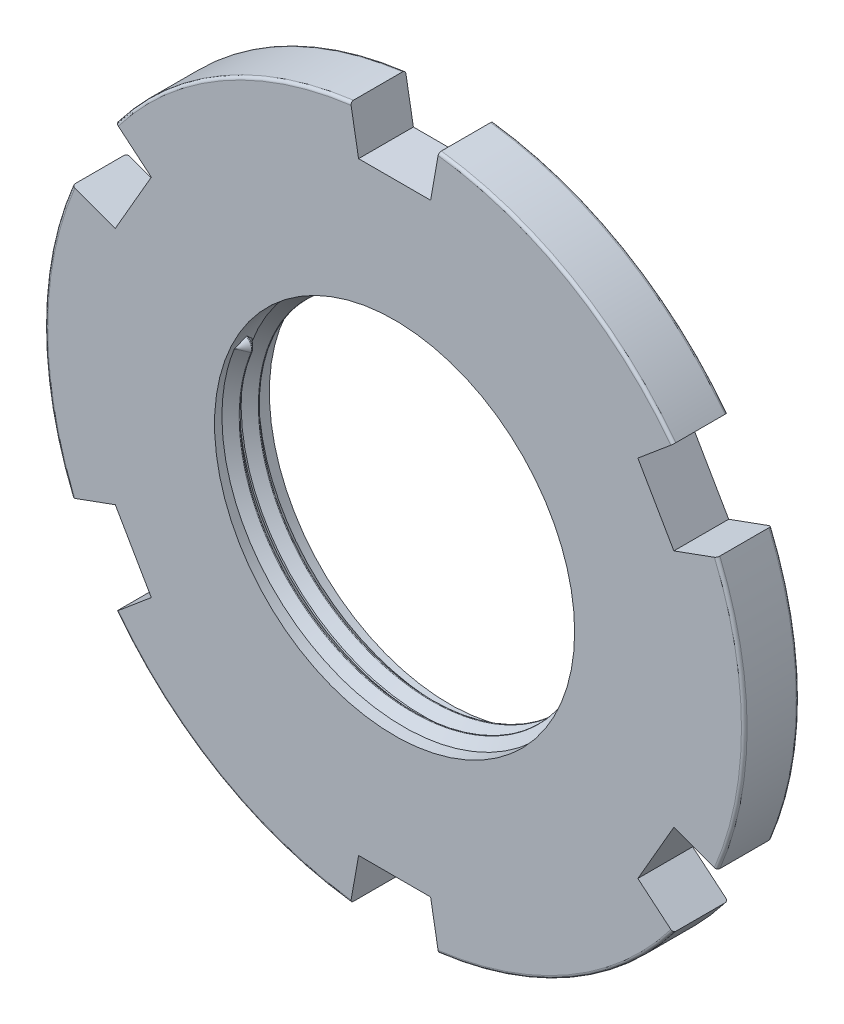
SolidWorks part; units mm, degrees
ref_plane "Plan de face" through (0, 0, 0) normal (0, 0, 1) x (1, 0, 0)
ref_plane "Plan de dessus" through (0, 0, 0) normal (0, 1, 0) x (1, 0, 0)
ref_plane "Plan de droite" through (0, 0, 0) normal (1, 0, 0) x (0, 0, -1)
sketch "Sketch1" plane through (0, 0, 0) normal (0, 0, 1) x (1, 0, 0)
  circle A0 centre (0, 0) radius 19.05
  circle A1 centre (0, 0) radius 37
  dimension "D1" = 74
  dimension "D2" = 38.1
extrude "Boss-Extrude1" add sketch "Sketch1" along normal blind 5.8
fillet "Fillet1" radius 0.3 2 edges at (37, 0, 0) (37, 0, 5.8)
sketch "Sketch2" plane through (0, 0, 5.8) normal (0, 0, 1) x (1, 0, 0)
  line L0 (0, 0) -> (0, 31.92) construction
  line L1 (-5.1536, 39.54) -> (5.1536, 39.54)
  line L2 (5.1536, 39.54) -> (3.81, 31.92)
  line L3 (3.81, 31.92) -> (-3.81, 31.92)
  line L4 (-3.81, 31.92) -> (-5.1536, 39.54)
  circle A2 centre (0, 0) radius 37 construction
  dimension "D1" = 7.62
  dimension "D2" = 5.08
  dimension "D3" = 7.62
  dimension "D4" = 100
  dimension "D5" = 100
extrude "Cut-Extrude1" cut sketch "Sketch2" against normal blind 7.8
pattern_circular "CirPattern1" count 6 over 360 about axis through (0, 0, 5.8) along (0, 0, 1) of "Cut-Extrude1"
ref_plane "Plane1" through (0, 0, 0.9525) normal (0, 0, 1) x (1, 0, 0)
sketch "Sketch3" plane through (0, 0, 0.9525) normal (0, 0, 1) x (1, 0, 0)
  circle A0 centre (0, 0) radius 19.05 construction
  circle A1 centre (0, 0) radius 19.05
curve "Helix/Spiral1" pitch 2.032 height 3.175 radius 19.05 left hand yes centre (0, 0, 0.9525) axis (0, 0, 1) start towards (1, 0, 0)
ref_plane "Plane2" through (19.05, 0, 0.9525) normal (0, -0.9999, 0.017) x (1, 0, 0)
sketch "Sketch4" plane through (19.05, 0, 0.9525) normal (0, -0.9999, 0.017) x (1, 0, 0)
  line B0 (0.0231, 1.0388) -> (0.0231, -0.8662)
  line B1 (0.0231, 1.0388) -> (-0.9337, 0.1419)
  line B2 (-0.9337, 0.0307) -> (0.0231, -0.8662)
  arc B3 (-0.9337, 0.0307) -> (-0.9337, 0.1419) centre (-0.8815, 0.0863) cw
sketch_block_instance "Block-lower body-3"
sketch_block "Block-lower body" parameters "D2"=0.0762, "D1"=1.905
sweep "Sweep1" add profiles "Sketch4" path "Helix/Spiral1"
sketch "Sketch5" plane through (0, -0.0162, 0.0003) normal (0, 0.9999, -0.017) x (1, 0, 0)
  line L3 (18.1163, -1.0942) -> (19.05, -1.9695)
  line L4 (19.05, -1.9695) -> (19.05, -0.1077)
  line L5 (19.05, -0.1077) -> (18.1163, -0.983)
  line L6 (18.1163, -1.0942) -> (19.05, -1.9695)
  line L7 (19.05, -1.9695) -> (19.05, -0.1077)
  line L8 (19.05, -0.1077) -> (18.1163, -0.983)
  arc A1 (18.1163, -0.983) -> (18.1163, -1.0942) centre (18.1685, -1.0386) ccw
  arc A2 (18.1163, -0.983) -> (18.1163, -1.0942) centre (18.1685, -1.0386) ccw
  dimension "D1" = 0
revolve "Revolve1" add sketch "Sketch5" angle 180 about L7
sketch "Sketch6" plane through (0.0268, 0.0647, 0.0012) normal (0.3826, 0.9237, 0.017) x (0.9239, -0.3826, -0.007)
  line L3 (-18.1451, -4.0305) -> (-19.0726, -3.1487)
  line L4 (-19.0726, -3.1487) -> (-19.0857, -5.0104)
  line L5 (-19.0857, -5.0104) -> (-18.1459, -4.1417)
  line L6 (-18.1451, -4.0305) -> (-19.0726, -3.1487)
  line L7 (-19.0726, -3.1487) -> (-19.0857, -5.0104)
  line L8 (-19.0857, -5.0104) -> (-18.1459, -4.1417)
  arc A1 (-18.1459, -4.1417) -> (-18.1451, -4.0305) centre (-18.1976, -4.0857) ccw
  arc A2 (-18.1459, -4.1417) -> (-18.1451, -4.0305) centre (-18.1976, -4.0857) ccw
  dimension "D1" = 0
revolve "Revolve2" add sketch "Sketch6" angle 180 about L7
